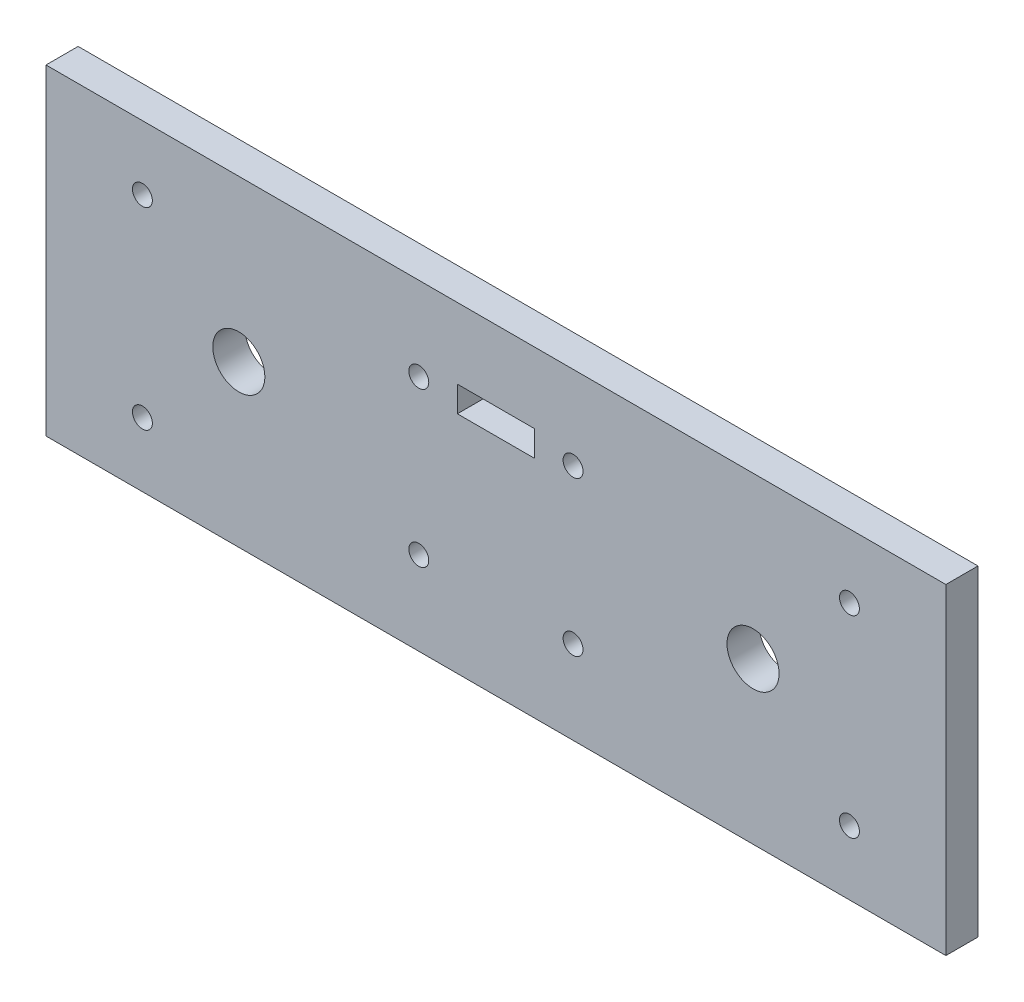
SolidWorks part; units mm, degrees
ref_plane "Plan de face" through (0, 0, 0) normal (0, 0, 1) x (1, 0, 0)
ref_plane "Plan de dessus" through (0, 0, 0) normal (0, 1, 0) x (1, 0, 0)
ref_plane "Plan de droite" through (0, 0, 0) normal (1, 0, 0) x (0, 0, -1)
sketch "Esquisse1" plane through (0, 0, 0) normal (0, 0, 1) x (1, 0, 0)
  line L0 (0, 0) -> (10.6959, 0) construction
  line L1 (-70, -25) -> (70, -25)
  line L2 (-70, -25) -> (-70, 25)
  line L3 (-70, 25) -> (70, 25)
  line L4 (70, -25) -> (70, 25)
  line L5 (-70, -25) -> (70, 25) construction
  line L6 (-70, 25) -> (70, -25) construction
  line L11 (0, 12) -> (0, 0) construction
  line L12 (-6, 10) -> (6, 10)
  line L13 (0, 0) -> (0, -12.4048) construction
  line L14 (-6, 10) -> (-6, 14)
  line L15 (-6, 14) -> (6, 14)
  line L16 (6, 10) -> (6, 14)
  line L17 (-6, 10) -> (6, 14) construction
  line L18 (-6, 14) -> (6, 10) construction
  circle A0 centre (-40, 0) radius 4.05
  circle A6 centre (-55, -15) radius 1.55
  circle A7 centre (-55, 15) radius 1.55
  circle A8 centre (55, -15) radius 1.55
  circle A9 centre (55, 15) radius 1.55
  circle A10 centre (40, 0) radius 4.05
  circle A11 centre (-12, 12) radius 1.55
  circle A12 centre (-12, -12) radius 1.55
  circle A13 centre (12, -12) radius 1.55
  circle A14 centre (12, 12) radius 1.55
  point P0 (0, 0)
  point P5 (0, 0)
  point P8 (0, 12)
  point P36 (0, 0)
  dimension "D3" = 15
  dimension "D4" = 10
  dimension "D5" = 8.1
  dimension "D6" = 3.1
  dimension "D7" = 3.1
  dimension "D1" = 140
  dimension "D2" = 50
  dimension "D8" = 12
  dimension "D9" = 40
  dimension "D10" = 12
  dimension "D11" = 12
  dimension "D12" = 4
  dimension "D13" = 12
  dimension "D14" = 25
extrude "Boss.-Extru.1" add sketch "Esquisse1" against normal blind 5
